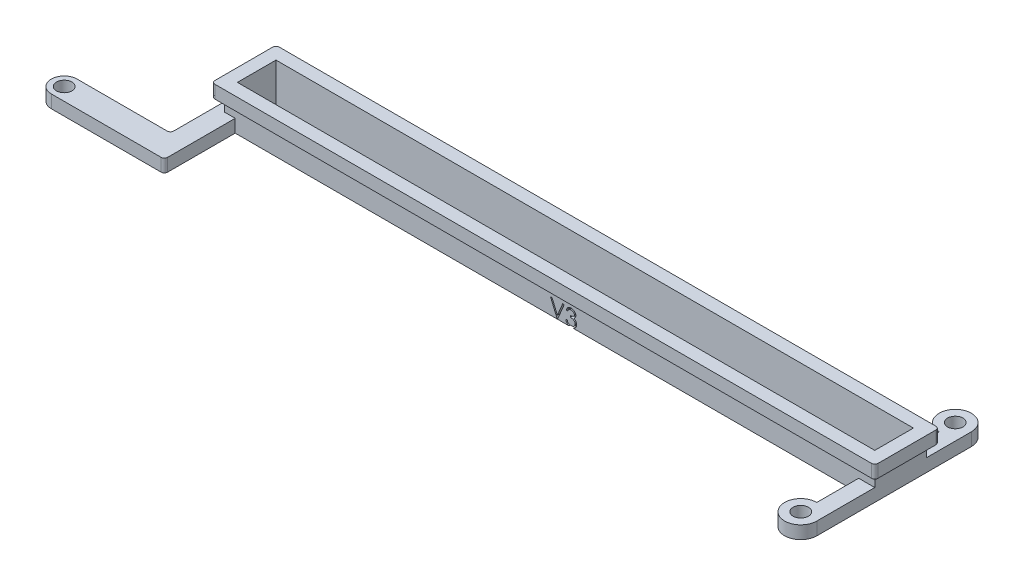
SolidWorks part; units mm, degrees
ref_plane "Front Plane" through (0, 0, 0) normal (0, 0, 1) x (1, 0, 0)
ref_plane "Top Plane" through (0, 0, 0) normal (0, 1, 0) x (1, 0, 0)
ref_plane "Right Plane" through (0, 0, 0) normal (1, 0, 0) x (0, 0, -1)
sketch "Sketch1" plane through (0, 0, 0) normal (0, 1, 0) x (1, 0, 0)
  line L0 (-50.5, 4) -> (-50.5, -4)
  line L1 (-49.5, 3) -> (49.5, 3)
  line L2 (-49.5, 3) -> (-49.5, -3)
  line L3 (-49.5, -3) -> (49.5, -3)
  line L4 (49.5, 3) -> (49.5, -3)
  line L5 (-49.5, 3) -> (49.5, -3) construction
  line L6 (-49.5, -3) -> (49.5, 3) construction
  line L7 (-50.5, -4) -> (50.5, -4)
  line L8 (50.5, 4) -> (50.5, -4)
  line L9 (-50.5, 4) -> (50.5, 4)
  point P0 (0, 0)
  dimension "D1" = 6
  dimension "D2" = 99
  dimension "D3" = 1
extrude "Boss-Extrude1" add sketch "Sketch1" along normal blind 10
sketch "Sketch2" plane through (0, 0, 0) normal (0, -1, 0) x (1, 0, 0)
  line L0 (0, 0) -> (74.3491, 0) construction
  line L1 (48, 0) -> (48, 10.5) construction
  line L2 (50.5, 4) -> (50.5, -4) construction
  line L4 (50.5, 4) -> (67.4224, 4) construction
  line L5 (50.5, -4) -> (69.4178, -4) construction
  line L7 (48, 4) -> (50.5, 4)
  line L9 (48, -4) -> (50.5, -4)
  line L11 (48, 0) -> (48, -8.5) construction
  line L15 (50.5, 4) -> (50.5, 13)
  line L16 (50.5, 13) -> (50, 13) construction
  line L17 (50.5, -4) -> (50.5, -11)
  line L18 (50.5, -11) -> (50, -11) construction
  line L19 (48, 10.5) -> (48, 4)
  line L20 (48, -8.5) -> (48, -4)
  line L21 (-50.5, 4) -> (-50.5, 13) construction
  line L22 (-50.5, 13) -> (-64.4, 13) construction
  line L23 (-66.4, 15) -> (-48.8351, 15)
  line L24 (-48.8351, 15) -> (-48.8351, 4)
  line L25 (-50.5, 4) -> (50.5, 4) construction
  line L26 (-66.4, 11) -> (-51.9017, 11)
  line L27 (-50.5, -4) -> (-59.3527, -4) construction
  line L28 (-51.9017, 11) -> (-51.9017, -4)
  line L29 (-51.9017, -4) -> (-50.5, -4)
  line L30 (-50.5, -4) -> (-50.5, 4)
  line L31 (-50.5, 4) -> (-48.8351, 4)
  line L32 (-64.4, 13) -> (-65.2, 13) construction
  line L33 (-65.2, 13) -> (-66.4, 13) construction
  line L34 (48, 10.5) -> (48, 11) construction
  line L35 (48, 11) -> (48, 13) construction
  line L36 (48, 11) -> (48, 10.5) construction
  line L37 (48, -8.5) -> (48, -9) construction
  line L38 (48, -9) -> (48, -11) construction
  line L39 (48, -9) -> (48, -8.5) construction
  circle A0 centre (48, 13) radius 1.2
  circle A4 centre (48, -11) radius 1.2
  arc A5 (50.5, -11) -> (48, -8.5) centre (48, -11) ccw construction
  arc A8 (48, 10.5) -> (50.5, 13) centre (48, 13) ccw construction
  circle A10 centre (-66.4, 13) radius 1.2
  arc A11 (-66.4, 15) -> (-66.4, 11) centre (-66.4, 13) ccw
  arc A12 (-64.4, 13) -> (-66.4, 15) centre (-66.4, 13) ccw construction
  arc A13 (-66.4, 11) -> (-64.4, 13) centre (-66.4, 13) ccw construction
  arc A14 (50.5, 13) -> (48, 10.5) centre (48, 13) ccw
  arc A15 (48, -8.5) -> (50.5, -11) centre (48, -11) ccw
  dimension "D3" = 2.4
  dimension "D9" = 2.4
  dimension "D10" = 4
  dimension "D1" = 2.5
  dimension "D2" = 13
  dimension "D5" = 11
  dimension "D7" = 9
  dimension "D8" = 15.9
extrude "Boss-Extrude2" add sketch "Sketch2" against normal blind 2
sketch "Sketch3" plane through (0, 10, 0) normal (0, 1, 0) x (1, 0, 0)
  line L0 (51.5, 5) -> (-51.5, 5)
  line L1 (-51.5, 5) -> (-51.5, -5)
  line L2 (-51.5, -5) -> (51.5, -5)
  line L3 (51.5, -5) -> (51.5, 5)
  line L4 (50.5, 4) -> (-50.5, 4)
  line L5 (-50.5, 4) -> (-50.5, -4)
  line L6 (-50.5, -4) -> (50.5, -4)
  line L7 (50.5, -4) -> (50.5, 4)
  line L8 (50.5, 4) -> (-50.5, 4)
  line L9 (-50.5, 4) -> (-50.5, -4)
  line L10 (-50.5, -4) -> (50.5, -4)
  line L11 (50.5, -4) -> (50.5, 4)
  dimension "D1" = 0
  dimension "D2" = 1
extrude "Boss-Extrude3" add sketch "Sketch3" against normal blind 6
fillet "Fillet4" radius 1 1 edges at (0, 4, -4)
fillet "Fillet5" radius 1 1 edges at (0, 4, 4)
fillet "Fillet6" radius 1 1 edges at (50.5, 4, 0)
fillet "Fillet7" radius 1 1 edges at (-50.5, 4, 0)
fillet "Fillet8" radius 0.5 2 edges at (-48.8351, 1, 15) (-51.9017, 1, 11)
fillet "Fillet9" radius 0.5 4 edges at (51.5, 7, -5) (51.5, 7, 5) (-51.5, 7, 5) (-51.5, 7, -5)
sketch "Sketch4" plane through (0, 10, 0) normal (0, 1, 0) x (1, 0, 0)
  line L4 (51.5, -4.5) -> (51.5, 4.5)
  line L5 (51, 5) -> (-51, 5)
  line L6 (-51.5, 4.5) -> (-51.5, -4.5)
  line L7 (-51, -5) -> (51, -5)
  line L8 (51.5, -4.5) -> (51.5, 4.5)
  line L9 (51, 5) -> (-51, 5)
  line L10 (-51.5, 4.5) -> (-51.5, -4.5)
  line L11 (-51, -5) -> (51, -5)
  arc A4 (51.5, 4.5) -> (51, 5) centre (51, 4.5) ccw
  arc A5 (-51, 5) -> (-51.5, 4.5) centre (-51, 4.5) ccw
  arc A6 (-51.5, -4.5) -> (-51, -5) centre (-51, -4.5) ccw
  arc A7 (51, -5) -> (51.5, -4.5) centre (51, -4.5) ccw
  arc A8 (51.5, 4.5) -> (51, 5) centre (51, 4.5) ccw
  arc A9 (-51, 5) -> (-51.5, 4.5) centre (-51, 4.5) ccw
  arc A10 (-51.5, -4.5) -> (-51, -5) centre (-51, -4.5) ccw
  arc A11 (51, -5) -> (51.5, -4.5) centre (51, -4.5) ccw
  dimension "D1" = 0
extrude "Cut-Extrude1" cut sketch "Sketch4" against normal blind 4
sketch "Sketch5" plane through (0, 0, 4) normal (0, 0, 1) x (1, 0, 0)
  text T0 "V3" font "Century Gothic" height 2.5
  point P1 (0, 0.4649)
  point P2 (0, 0)
  point P4 (0, 0)
  point P5 (0, 0)
extrude "Cut-Extrude2" cut sketch "Sketch5" against normal blind 0.5
